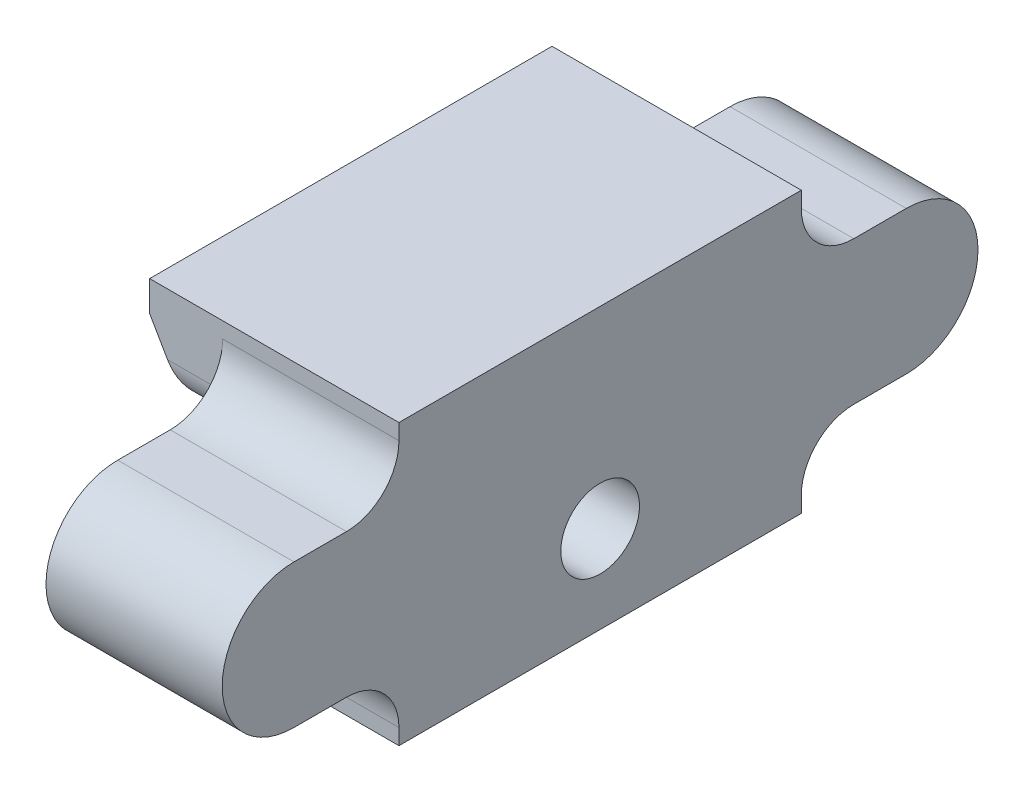
SolidWorks part; units mm, degrees
material "Сплав 2024"
ref_plane "Спереди" through (0, 0, 0) normal (0, 0, 1) x (1, 0, 0)
ref_plane "Сверху" through (0, 0, 0) normal (0, 1, 0) x (1, 0, 0)
ref_plane "Справа" through (0, 0, 0) normal (1, 0, 0) x (0, 0, -1)
sketch "Эскиз1" plane through (0, 0, 0) normal (0, 0, 1) x (1, 0, 0)
  line L1 (0, 0) -> (-10.0746, 0)
  line L2 (-12.0746, 10.5) -> (-15.25, 16)
  line L3 (-15.25, 16) -> (0, 16)
  line L4 (0, 16) -> (0, 0)
  line L5 (-12.0746, 10.5) -> (-10.0746, 10.5)
  line L6 (-10.0746, 10.5) -> (-10.0746, 0)
  dimension "D1" = 2
  dimension "D2" = 5.5
  dimension "D3" = 15.25
  dimension "D4" = 60
  dimension "D6" = 16
extrude "Бобышка-Вытянуть1" add sketch "Эскиз1" along normal blind 23
sketch "Эскиз2" plane through (-10.0746, 0, 0) normal (1, 0, 0) x (0, 0, -1)
  line L0 (-23, 5) -> (0, 5) construction
  line L1 (-23, 0) -> (-23, 16) construction
  line L2 (0, 0) -> (0, 16) construction
  line L3 (-23, 0) -> (0, 0) construction
  line L4 (-19, 0) -> (-19, 16) construction
  line L5 (-23, 16) -> (0, 16) construction
  line L6 (-4, 16) -> (-4, 0) construction
  line L7 (-11.5, 16) -> (-11.5, 0) construction
  circle A0 centre (-19, 5) radius 2.5
  circle A1 centre (-4, 5) radius 2.5
  dimension "D4" = 5
  dimension "D1" = 5
  dimension "D2" = 7.5
extrude "Вырез-Вытянуть1" cut sketch "Эскиз2" along normal blind 4 and the other way through all
hole_wizard "Отверстие с зазором M41" positions "Эскиз4" profile "Эскиз3" hole size "M4" standard "Din" end condition through all
sketch "Эскиз4" plane through (0, 1.5428, 4.5254) normal (-1, 0, 0) x (0, 0, 1)
  line L0 (18.4746, 3.4572) -> (-4.5254, 3.4572) construction
  line L1 (6.9746, 14.4572) -> (6.9746, -1.5428) construction
  point P0 (6.9746, 3.4572)
sketch "Эскиз3" plane through (0, 5, 11.5) normal (0, 1, 0) x (0, 0, -1)
  line L0 (0, 0) -> (0, 15.25)
  line L1 (0, 15.25) -> (2.25, 15.25)
  line L2 (2.25, 15.25) -> (2.25, 0)
  line L5 (2.25, 0) -> (0, 0)
  line L11 (0, -6.35) -> (0, 107.95) construction
  dimension "Диаметр сквозного отверстия" = 4.5
  dimension "Глубина сквозного отверстия" = 15.25
chamfer "Фаска1" distance 1 angle 90 1 edges at (-15.25, 16, 11.5) first distance on face at (-7.625, 16, 11.5)
sketch "Эскиз7" plane through (0, 0, 0) normal (-1, 0, 0) x (0, 0, 1)
  line L0 (23, 8) -> (0, 8) construction
  line L2 (-6, 12.1) -> (0, 12.1)
  line L3 (0, 10.5) -> (0, 0) construction
  line L4 (0, 12.1) -> (0, 3.9)
  line L5 (0, 3.9) -> (-6, 3.9)
  line L6 (11.5, 0) -> (11.5, 9.35) construction
  line L7 (23, 0) -> (0, 0) construction
  line L8 (23, 0) -> (23, 16) construction
  line L9 (23, 12.1) -> (23, 3.9)
  line L10 (29, 12.1) -> (23, 12.1)
  line L11 (23, 3.9) -> (29, 3.9)
  arc A0 (-6, 12.1) -> (-6, 3.9) centre (-6, 8) ccw
  arc A1 (29, 12.1) -> (29, 3.9) centre (29, 8) cw
  point P8 (0, 8)
  dimension "D2" = 4.1
  dimension "D1" = 6
extrude "Бобышка-Вытянуть2" add sketch "Эскиз7" along normal up to surface (10.0746 mm away) up to face at (-10.0746, 7.25, 11.5)
fillet "Скругление1" radius 3 4 edges
fillet "Скругление2" radius 2 2 edges
sketch "Эскиз11" plane through (-10.0746, 0, 0) normal (-1, 0, 0) x (0, 0, 1)
  line L0 (-10.1, 12.8239) -> (-10.1, 1.9255) construction
  line L1 (23, 0) -> (0, 0) construction
  arc A0 (-6, 12.1) -> (-6, 3.9) centre (-6, 8) ccw construction
  point P5 (-10.1, 0)
